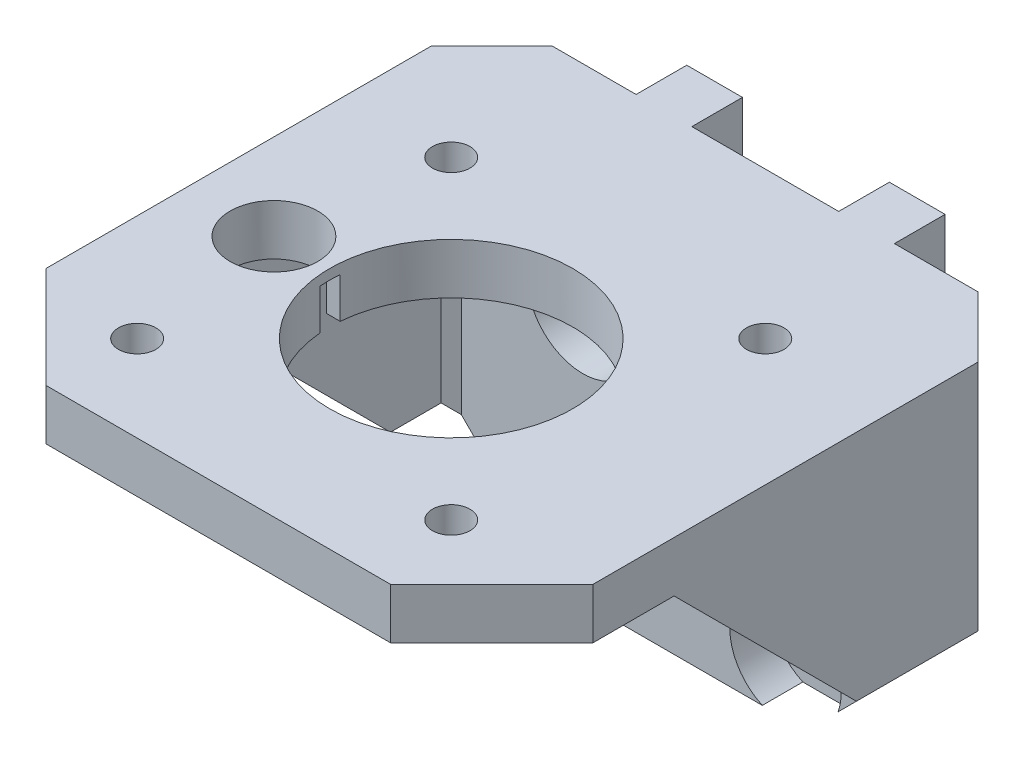
SolidWorks part; units mm, degrees
ref_plane "Front Plane" through (0, 0, 0) normal (0, 0, 1) x (1, 0, 0)
ref_plane "Top Plane" through (0, 0, 0) normal (0, 1, 0) x (1, 0, 0)
ref_plane "Right Plane" through (0, 0, 0) normal (1, 0, 0) x (0, 0, -1)
sketch "Sketch1" plane through (0, 0, 0) normal (0, 1, 0) x (1, 0, 0)
  line L1 (-27, 27) -> (27, 27)
  line L2 (-27, 27) -> (-27, -27)
  line L3 (-27, -27) -> (27, -27)
  line L4 (27, 27) -> (27, -27)
  line L5 (-27, 27) -> (27, -27) construction
  line L6 (-27, -27) -> (27, 27) construction
  point P0 (0, 0)
  dimension "D1" = 54
  dimension "D2" = 54
extrude "Boss-Extrude1" add sketch "Sketch1" along normal blind 5
sketch "Sketch3" plane through (0, 0, -27) normal (0, 0, -1) x (-1, 0, 0)
  line L0 (27, 5) -> (27, 0) construction
  line L1 (-27, 5) -> (27, 5)
  line L2 (-27, 5) -> (-27, -33)
  line L3 (-27, -33) -> (27, -33)
  line L4 (27, 5) -> (27, -33)
  dimension "D1" = 38
extrude "Boss-Extrude2" add sketch "Sketch3" against normal blind 8
sketch "Sketch9" plane through (0, 5, 0) normal (0, 1, 0) x (1, 0, 0)
  line L0 (27, 27) -> (-27, 27) construction
  line L1 (12.75, 27) -> (7.25, 27)
  line L2 (12.75, 27) -> (12.75, 32)
  line L3 (12.75, 32) -> (7.25, 32)
  line L4 (7.25, 27) -> (7.25, 32)
  line L6 (-7.25, 27) -> (-12.75, 27)
  line L7 (-7.25, 27) -> (-7.25, 32)
  line L8 (-7.25, 32) -> (-12.75, 32)
  line L9 (-12.75, 27) -> (-12.75, 32)
  line L10 (-27, 27) -> (-27, -27) construction
  point P10 (-10, 32)
  point P11 (10, 32)
  dimension "D1" = 20
  dimension "D2" = 5
  dimension "D3" = 17
  dimension "D4" = 5.5
extrude "Boss-Extrude3" add sketch "Sketch9" against normal blind 7
sketch "Sketch2" plane through (0, 5, 0) normal (0, 1, 0) x (1, 0, 0)
  line L0 (-16.5, 12.5) -> (14.5, -18.5) construction
  line L1 (14.5, 12.5) -> (-16.5, -18.5) construction
  line L3 (-27, 27) -> (-27, -27) construction
  line L5 (27, 27) -> (12.75, 27) construction
  circle A0 centre (-1, -3) radius 12
  circle A1 centre (-18.5, -3) radius 4.325
  circle A2 centre (14.5, 12.5) radius 1.85
  circle A3 centre (-16.5, 12.5) radius 1.85
  circle A4 centre (-16.5, -18.5) radius 1.85
  circle A5 centre (14.5, -18.5) radius 1.85
  point P6 (-1, -3)
  dimension "D1" = 24
  dimension "D2" = 8.65
  dimension "D6" = 3.7
  dimension "D3" = 17.5
  dimension "D7" = 26
  dimension "D8" = 30
  dimension "D9" = 31
  dimension "D4" = 2
  dimension "D5" = 2
extrude "Cut-Extrude1" cut sketch "Sketch2" against normal blind 5
sketch "Sketch4" plane through (0, 0, -19) normal (0, 0, 1) x (1, 0, 0)
  line L0 (-27, 5) -> (-27, -33) construction
  line L1 (27, 5) -> (12.75, 5) construction
  circle A0 centre (-10, -8) radius 2.575
  circle A1 centre (10, -8) radius 2.575
  circle A2 centre (10, -28) radius 2.575
  circle A3 centre (-10, -28) radius 2.575
  dimension "D3" = 5.15
  dimension "D1" = 20
  dimension "D2" = 20
  dimension "D4" = 17
  dimension "D5" = 13
extrude "Cut-Extrude2" cut sketch "Sketch4" against normal blind 8
sketch "Sketch7" plane through (0, 0, -19) normal (0, 0, 1) x (1, 0, 0)
  circle A0 centre (-10, -8) radius 5.5
  circle A1 centre (10, -8) radius 5.5
  circle A2 centre (10, -28) radius 5.5
  circle A3 centre (-10, -28) radius 5.5
  dimension "D1" = 11
extrude "Cut-Extrude3" cut sketch "Sketch7" against normal blind 4
sketch "Sketch8" plane through (0, 0, 0) normal (0, -1, 0) x (1, 0, 0)
  line L1 (-16.0213, 2) -> (-11.5349, 2)
  line L2 (-16.0213, 2) -> (-16.0213, 4)
  line L3 (-16.0213, 4) -> (-11.5349, 4)
  line L4 (-11.5349, 2) -> (-11.5349, 4)
  line L5 (-16.0213, 2) -> (-11.5349, 4) construction
  line L6 (-16.0213, 4) -> (-11.5349, 2) construction
  point P0 (-13.7781, 3)
  dimension "D1" = 2
extrude "Cut-Extrude4" cut sketch "Sketch8" against normal blind 4
sketch "Sketch5" plane through (-27, 0, 0) normal (-1, 0, 0) x (0, 0, 1)
  line L0 (9, 0) -> (-19, -28)
  line L2 (-19, -33) -> (-19, 0) construction
  line L3 (-19, 0) -> (27, 0) construction
  dimension "D1" = 28
  dimension "D2" = 28
sketch "Sketch6" plane through (27, 0, 0) normal (1, 0, 0) x (0, 0, -1)
  line L0 (-9, 0) -> (19, -28)
  line L1 (-27, 0) -> (19, 0) construction
  line L2 (19, 0) -> (19, -33) construction
  dimension "D1" = 28
  dimension "D2" = 28
rib "Rib1" sketch "Sketch5" sketch "Sketch5" thickness 4 extrusion direction parallel to sketch draft on no parameters "D1"=4
rib "Rib9" sketch "Sketch6" sketch "Sketch6" thickness 6 extrusion direction parallel to sketch draft on no parameters "D1"=6
chamfer "Chamfer1" distance 10 angle 45 2 edges at (27, 2.5, 27) (-27, 2.5, 27)
chamfer "Chamfer2" distance 15 angle 45 1 edges at (27, -33, -23)
chamfer "Chamfer3" distance 15 angle 45 1 edges at (-27, -33, -23)
chamfer "Chamfer4" distance 1 angle 45 2 edges at (21, -12, -19) (-23, -11, -19)
chamfer "Chamfer6" distance 6 angle 45 2 edges at (-27, -6.5, -27) (27, -6.5, -27)
pattern_linear "LPattern2" count 2 spacing 19.5 along (0, -1, 0) of "Boss-Extrude3"
chamfer "Chamfer7" distance 2 angle 45 2 edges at (-10, -2, -32) (10, -2, -32)
chamfer "Chamfer8" distance 5 angle 45 2 edges at (10, -14.5, -32) (-10, -14.5, -32)
mirror "Mirror1" [suppressed] of bodies 106 104
delete or keep bodies "Body-Delete/Keep 1" [suppressed] type delete bodies bodies 106
